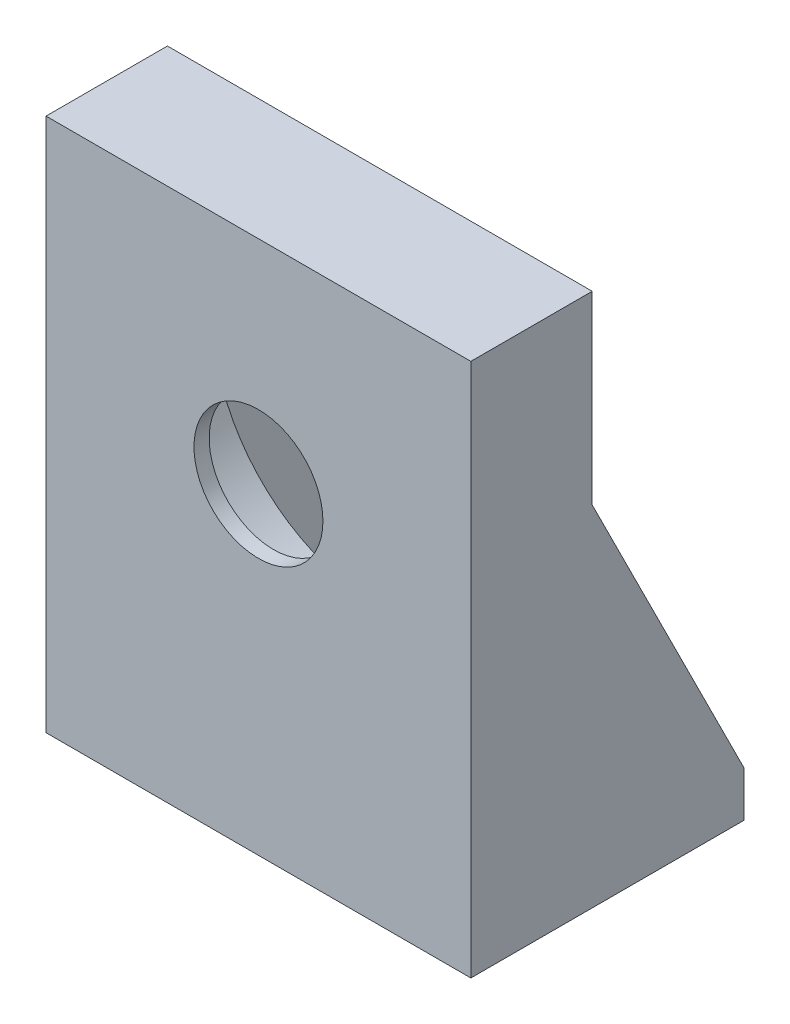
SolidWorks part; units mm, degrees
ref_plane "Front Plane" through (0, 0, 0) normal (0, 0, 1) x (1, 0, 0)
ref_plane "Top Plane" through (0, 0, 0) normal (0, 1, 0) x (1, 0, 0)
ref_plane "Right Plane" through (0, 0, 0) normal (1, 0, 0) x (0, 0, -1)
sketch "Sketch2" plane through (0, 0, -2.5384) normal (0, 0, 1) x (1, 0, 0)
  line L1 (-92.7321, 37.036) -> (-64.7321, 37.036)
  line L2 (-92.7321, 37.036) -> (-92.7321, 1.836)
  line L3 (-92.7321, 1.836) -> (-64.7321, 1.836)
  line L4 (-64.7321, 37.036) -> (-64.7321, 1.836)
  line L5 (-92.7321, 37.036) -> (-64.7321, 1.836) construction
  line L6 (-92.7321, 1.836) -> (-64.7321, 37.036) construction
  line L8 (271.6524, 1.836) -> (-80.3476, 1.836) construction
  line L9 (-78.7321, 37.036) -> (-78.7321, 1.836) construction
  circle A0 centre (-78.7321, 23.036) radius 11
  circle A1 centre (-78.7321, 23.036) radius 4.25
  circle A4 centre (-78.7321, 23.036) radius 4 construction
  point P11 (-78.7321, 19.436)
  circle M1 centre (-78.7321, 23.036) radius 9.65
  circle M2 centre (-78.7321, 23.036) radius 10.7
  dimension "D1" = 22
  dimension "D2" = 8.5
  dimension "D3" = 14
  dimension "D4" = 14
extrude "Boss-Extrude3" add sketch "Sketch2" against normal up to surface (7 mm away) separate body contours L4 L1 L2 L3 A0 region at (-78.7321, 36.5862, -2.5384)
sketch "Sketch3" plane through (-92.7321, 0, 0) normal (-1, 0, 0) x (0, 0, 1)
  line L0 (-9.5384, 1.836) -> (-19.5384, 1.836)
  line L1 (-19.5384, 1.836) -> (-19.5384, 4.836)
  line L2 (-19.5384, 4.836) -> (-9.5384, 24.836)
  line L3 (-9.5384, 1.836) -> (-9.5384, 37.036) construction
  line L5 (-19.5384, 4.836) -> (-9.5384, 4.836)
  line L6 (-9.5384, 4.836) -> (-9.5384, 1.836)
  line L7 (-9.5384, 24.836) -> (-9.5384, 4.836)
  line M3 (-9.5384, 37.036) -> (-9.5384, 1.836)
  dimension "D1" = 3
  dimension "D2" = 20
  dimension "D3" = 10
extrude "Boss-Extrude4" add sketch "Sketch3" against normal up to surface (28 mm away) contours L5 L1 L0 M3 region at (-92.7321, 3.336, -14.5384) up to face at (-64.7321, 19.436, -6.0384)
extrude "Boss-Extrude5" add sketch "Sketch3<3>" against normal blind 3 contours L2 L5 M3 region at (-92.7321, 11.5026, -12.8718)
sketch "Sketch3<3>" plane through (-92.7321, 0, 0) normal (-1, 0, 0) x (0, 0, 1) same geometry as "Sketch3"
extrude "Boss-Extrude6" add sketch "Sketch3<4>" along normal blind 3 from surface contours L2 L5 M3 region at (-92.7321, 11.5026, -12.8718) starting at face at (-64.7321, 14.5693, -10.5384)
sketch "Sketch3<4>" plane through (-92.7321, 0, 0) normal (-1, 0, 0) x (0, 0, 1) same geometry as "Sketch3"
sketch "Sketch4" plane through (0, 4.836, 0) normal (0, 1, 0) x (1, 0, 0)
  line L0 (-67.7321, 14.5384) -> (-89.7321, 14.5384) construction
  line L1 (-67.7321, 19.5384) -> (-67.7321, 9.5384) construction
  line L2 (-89.7321, 19.5384) -> (-89.7321, 9.5384) construction
  line L3 (-78.7321, 9.5384) -> (-78.7321, 19.5384) construction
  line L4 (-67.7321, 9.5384) -> (-89.7321, 9.5384) construction
  line L5 (-67.7321, 19.5384) -> (-89.7321, 19.5384) construction
  line L6 (-67.7321, 14.5384) -> (-78.7321, 14.5384) construction
  line L7 (-78.7321, 14.5384) -> (-89.7321, 14.5384) construction
  circle A0 centre (-72.7321, 14.5384) radius 2
  circle A1 centre (-72.7321, 14.5384) radius 3.5 construction
  circle A2 centre (-84.7321, 14.5384) radius 3.5 construction
  circle A3 centre (-84.7321, 14.5384) radius 2
  dimension "D1" = 4
  dimension "D2" = 7
  dimension "D3" = 6
extrude "Cut-Extrude1" cut sketch "Sketch4" against normal through all
extrude "Boss-Extrude7" add sketch "Sketch2<3>" along normal blind 1 contours L4 L1 L2 L3 A0 | A1 M1 | M2 M1 | A0 M2 region at (-78.7321, 36.5862, -2.5384) region at (-89.701, 23.036, -2.5384) region at (-88.1092, 23.036, -2.5384) region at (-89.1295, 23.036, -2.5384)
sketch "Sketch2<3>" plane through (0, 0, -2.5384) normal (0, 0, 1) x (1, 0, 0) same geometry as "Sketch2"
